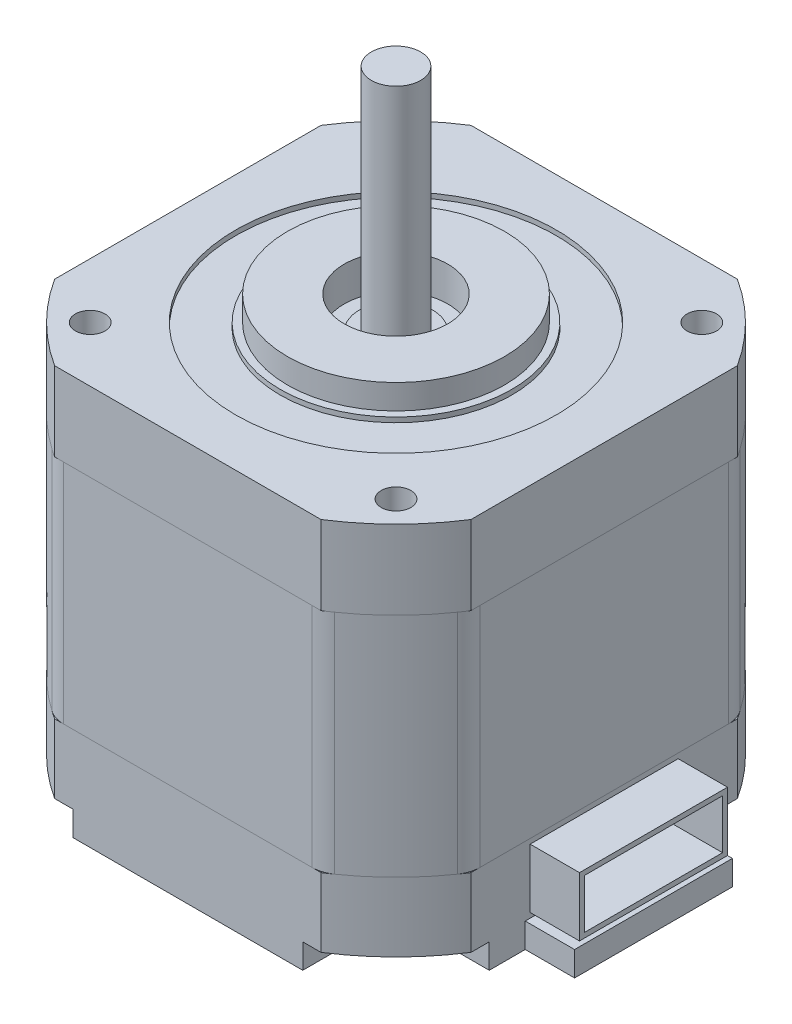
SolidWorks part; units mm, degrees
ref_plane "Alzado" through (0, 0, 0) normal (0, 0, 1) x (1, 0, 0)
ref_plane "Planta" through (0, 0, 0) normal (0, 1, 0) x (1, 0, 0)
ref_plane "Vista lateral" through (0, 0, 0) normal (1, 0, 0) x (0, 0, -1)
sketch "Croquis1" plane through (0, 0, 0) normal (0, 1, 0) x (1, 0, 0)
  line L0 (13.5, 21.1) -> (-13.5, 21.1)
  line L2 (-21.1, 13.5) -> (-21.1, -13.5)
  line L4 (-13.5, -21.1) -> (13.5, -21.1)
  line L6 (21.1, -13.5) -> (21.1, 13.5)
  arc A0 (-13.5, 21.1) -> (-21.1, 13.5) centre (0, 0) ccw
  arc A1 (13.5, 21.1) -> (21.1, 13.5) centre (0, 0) cw
  arc A2 (21.1, -13.5) -> (13.5, -21.1) centre (0, 0) cw
  arc A3 (-21.1, -13.5) -> (-13.5, -21.1) centre (0, 0) ccw
  point P4 (-21.1, 0)
  point P10 (0, 21.1)
  dimension "D2" = 27
  dimension "D1" = 42.2
extrude "Saliente-Extruir1" add sketch "Croquis1" along normal mid plane 23
sketch "Croquis2" plane through (0, 11.5, 0) normal (0, 1, 0) x (1, 0, 0)
  line L12 (13.5003, 21.101) -> (-13.5003, 21.101)
  line L13 (-21.101, 13.5003) -> (-21.101, -13.5003)
  line L14 (-13.5003, -21.101) -> (13.5003, -21.101)
  line L15 (21.101, -13.5003) -> (21.101, 13.5003)
  line L16 (13.5003, 21.101) -> (-13.5003, 21.101)
  line L17 (-21.101, 13.5003) -> (-21.101, -13.5003)
  line L18 (-13.5003, -21.101) -> (13.5003, -21.101)
  line L19 (21.101, -13.5003) -> (21.101, 13.5003)
  arc A12 (21.101, 13.5003) -> (13.5003, 21.101) centre (0, 0) ccw
  arc A13 (-13.5003, 21.101) -> (-21.101, 13.5003) centre (0, 0) ccw
  arc A14 (-21.101, -13.5003) -> (-13.5003, -21.101) centre (0, 0) ccw
  arc A15 (13.5003, -21.101) -> (21.101, -13.5003) centre (0, 0) ccw
  arc A16 (21.101, 13.5003) -> (13.5003, 21.101) centre (0, 0) ccw
  arc A17 (-13.5003, 21.101) -> (-21.101, 13.5003) centre (0, 0) ccw
  arc A18 (-21.101, -13.5003) -> (-13.5003, -21.101) centre (0, 0) ccw
  arc A19 (13.5003, -21.101) -> (21.101, -13.5003) centre (0, 0) ccw
  dimension "D1" = 0.001
fillet "Redondeo1" radius 3 8 edges at (-21.1, 0, -13.5) (-13.5, 0, -21.1) (13.5, 0, -21.1) (21.1, 0, -13.5) (-21.1, 0, 13.5) (-13.5, 0, 21.1) (13.5, 0, 21.1) (21.1, 0, 13.5)
extrude "Saliente-Extruir2" add sketch "Croquis2" along normal blind 8
sketch "Croquis3" plane through (0, -11.5, 0) normal (0, -1, 0) x (1, 0, 0)
  line L8 (-13.5003, -21.101) -> (13.5003, -21.101)
  line L9 (-21.101, 13.5003) -> (-21.101, -13.5003)
  line L10 (13.5003, 21.101) -> (-13.5003, 21.101)
  line L11 (21.101, -13.5003) -> (21.101, 13.5003)
  line L12 (-13.5003, -21.101) -> (13.5003, -21.101)
  line L13 (-21.101, 13.5003) -> (-21.101, -13.5003)
  line L14 (13.5003, 21.101) -> (-13.5003, 21.101)
  line L15 (21.101, -13.5003) -> (21.101, 13.5003)
  arc A8 (13.5003, -21.101) -> (21.101, -13.5003) centre (0, 0) ccw
  arc A9 (-21.101, -13.5003) -> (-13.5003, -21.101) centre (0, 0) ccw
  arc A10 (-13.5003, 21.101) -> (-21.101, 13.5003) centre (0, 0) ccw
  arc A11 (21.101, 13.5003) -> (13.5003, 21.101) centre (0, 0) ccw
  arc A12 (13.5003, -21.101) -> (21.101, -13.5003) centre (0, 0) ccw
  arc A13 (-21.101, -13.5003) -> (-13.5003, -21.101) centre (0, 0) ccw
  arc A14 (-13.5003, 21.101) -> (-21.101, 13.5003) centre (0, 0) ccw
  arc A15 (21.101, 13.5003) -> (13.5003, 21.101) centre (0, 0) ccw
  dimension "D1" = 0
extrude "Saliente-Extruir3" add sketch "Croquis3" along normal blind 9.5
sketch "Croquis4" plane through (0, 19.5, 0) normal (0, 1, 0) x (1, 0, 0)
  line L0 (-15.5, 15.5) -> (-15.5, 21.101) construction
  line L1 (-15.5, 15.5) -> (-21.101, 15.5) construction
  line L2 (-21.101, 13.5003) -> (-21.101, -13.5003) construction
  line L3 (13.5003, 21.101) -> (-13.5003, 21.101) construction
  line L4 (0, 0) -> (0, 21.101) construction
  line L5 (0, 0) -> (-21.101, 0) construction
  circle A0 centre (0, 0) radius 16.25
  circle A1 centre (0, 0) radius 11.75
  circle A2 centre (0, 0) radius 11
  circle A3 centre (-15.5, 15.5) radius 1.5
  circle A7 centre (-15.5, -15.5) radius 1.5
  circle A8 centre (15.5, -15.5) radius 1.5
  circle A9 centre (15.5, 15.5) radius 1.5
  dimension "D1" = 32.5
  dimension "D2" = 23.5
  dimension "D3" = 22
  dimension "D4" = 3
  dimension "D5" = 31
extrude "Cortar-Extruir1" cut sketch "Croquis4" against normal blind 0.5 contours A0 A1 region at (-15.7904, 19.5, 0)
extrude "Saliente-Extruir4" add sketch "Croquis4<3>" along normal blind 2.5 contours A2
sketch "Croquis4<3>" plane through (0, 19.5, 0) normal (0, 1, 0) x (1, 0, 0) same geometry as "Croquis4"
extrude "Cortar-Extruir2" cut sketch "Croquis4<4>" against normal blind 5.5 contours A3 | A9 | A8 | A7
sketch "Croquis4<4>" plane through (0, 19.5, 0) normal (0, 1, 0) x (1, 0, 0) same geometry as "Croquis4"
sketch "Croquis5" plane through (0, 22, 0) normal (0, 1, 0) x (1, 0, 0)
  circle A0 centre (0, 0) radius 5.25
  dimension "D1" = 10.5
extrude "Cortar-Extruir3" cut sketch "Croquis5" against normal blind 3.5
sketch "Croquis6" plane through (0, 18.5, 0) normal (0, 1, 0) x (1, 0, 0)
  circle A0 centre (0, 0) radius 2.5
  circle A1 centre (0, 0) radius 3.7
  dimension "D2" = 5
  dimension "D1" = 1.2
extrude "Saliente-Extruir5" add sketch "Croquis6" along normal blind 0.25
extrude "Saliente-Extruir6" add sketch "Croquis6<2>" along normal blind 23.5 contours A0 region at (0, 18.5, 0)
sketch "Croquis6<2>" plane through (0, 18.5, 0) normal (0, 1, 0) x (1, 0, 0) same geometry as "Croquis6"
sketch "Croquis7" plane through (0, -21, 0) normal (0, -1, 0) x (1, 0, 0)
  line L0 (-11.6503, 21.101) -> (-11.6503, 14.6503)
  line L1 (-21.101, 11.6503) -> (-14.6503, 11.6503)
  line L2 (-21.101, 0) -> (0, 0) construction
  line L3 (0, 0) -> (0, 21.101) construction
  line L4 (21.101, -13.5003) -> (21.101, 13.5003)
  line L5 (13.5003, 21.101) -> (-13.5003, 21.101)
  line L6 (-21.101, 13.5003) -> (-21.101, -13.5003)
  line L7 (-13.5003, -21.101) -> (13.5003, -21.101)
  line L9 (-11.6503, 21.101) -> (-13.5003, 21.101)
  line L10 (-21.101, 13.5003) -> (-21.101, 11.6503)
  line L12 (-21.101, 13.5003) -> (-21.101, -13.5003) construction
  line L13 (13.5003, 21.101) -> (-13.5003, 21.101) construction
  line L14 (-11.6503, -21.101) -> (-11.6503, -14.6503)
  line L15 (-21.101, -11.6503) -> (-14.6503, -11.6503)
  line L16 (-21.101, -13.5003) -> (-21.101, -11.6503)
  line L17 (-11.6503, -21.101) -> (-13.5003, -21.101)
  line L18 (11.6503, -21.101) -> (11.6503, -14.6503)
  line L19 (11.6503, -21.101) -> (13.5003, -21.101)
  line L20 (21.101, -13.5003) -> (21.101, -11.6503)
  line L21 (21.101, -11.6503) -> (14.6503, -11.6503)
  line L22 (11.6503, 21.101) -> (11.6503, 14.6503)
  line L23 (21.101, 11.6503) -> (14.6503, 11.6503)
  line L24 (21.101, 13.5003) -> (21.101, 11.6503)
  line L25 (11.6503, 21.101) -> (13.5003, 21.101)
  arc A0 (-11.6503, 14.6503) -> (-14.6503, 11.6503) centre (-14.6503, 14.6503) cw
  arc A1 (-11.6503, -14.6503) -> (-14.6503, -11.6503) centre (-14.6503, -14.6503) ccw
  arc A2 (-13.5003, -21.101) -> (-21.101, -13.5003) centre (0, 0) cw
  arc A3 (13.5003, -21.101) -> (21.101, -13.5003) centre (0, 0) ccw
  arc A4 (13.5003, -21.101) -> (21.101, -13.5003) centre (0, 0) ccw
  arc A5 (21.101, 13.5003) -> (13.5003, 21.101) centre (0, 0) ccw
  arc A6 (-13.5003, 21.101) -> (-21.101, 13.5003) centre (0, 0) ccw
  arc A7 (-21.101, -13.5003) -> (-13.5003, -21.101) centre (0, 0) ccw
  arc A10 (-13.5003, 21.101) -> (-21.101, 13.5003) centre (0, 0) ccw
  arc A12 (11.6503, -14.6503) -> (14.6503, -11.6503) centre (14.6503, -14.6503) cw
  arc A13 (11.6503, 14.6503) -> (14.6503, 11.6503) centre (14.6503, 14.6503) ccw
  arc A14 (13.5003, 21.101) -> (21.101, 13.5003) centre (0, 0) cw
  dimension "D3" = 3
  dimension "D2" = 1.85
  dimension "D1" = 0
extrude "Cortar-Extruir4" cut sketch "Croquis7" against normal blind 2.5
sketch "Croquis8" plane through (0, -18.5, 0) normal (0, -1, 0) x (1, 0, 0)
  circle A0 centre (15.5, -15.5) radius 1.5 construction
  circle A1 centre (-15.5, -15.5) radius 1.5 construction
  circle A2 centre (-15.5, 15.5) radius 1.5 construction
  circle A3 centre (15.5, 15.5) radius 1.5 construction
  circle A4 centre (15.5, -15.5) radius 1.5
  circle A5 centre (-15.5, -15.5) radius 1.5
  circle A6 centre (-15.5, 15.5) radius 1.5
  circle A7 centre (15.5, 15.5) radius 1.5
extrude "Cortar-Extruir5" cut sketch "Croquis8" against normal blind 15
sketch "Croquis9" plane through (0, -21, 0) normal (0, -1, 0) x (1, 0, 0)
  circle A2 centre (0, 0) radius 4.2
  circle A3 centre (0, 0) radius 4.2
  dimension "D1" = 0.5
extrude "Cortar-Extruir6" cut sketch "Croquis9" against normal blind 3
sketch "Croquis10" plane through (0, -18, 0) normal (0, -1, 0) x (1, 0, 0)
  circle A0 centre (0, 0) radius 2.5 construction
  circle A1 centre (0, 0) radius 3.7
  circle A2 centre (0, 0) radius 3.7
  circle A3 centre (0, 0) radius 2.5
  dimension "D1" = 0
extrude "Saliente-Extruir7" add sketch "Croquis10" along normal blind 0.25
extrude "Saliente-Extruir8" add sketch "Croquis10<2>" along normal blind 1.25 contours A3 region at (0, -18, 0)
sketch "Croquis10<2>" plane through (0, -18, 0) normal (0, -1, 0) x (1, 0, 0) same geometry as "Croquis10"
sketch "Croquis11" plane through (21.101, 0, 0) normal (1, 0, 0) x (0, 0, -1)
  line L0 (-12.5919, -11.5) -> (12.5919, -11.5) construction
  line L1 (8, -21) -> (-8, -21)
  line L2 (8, -21) -> (8, -18.5)
  line L3 (8, -18.5) -> (-8, -18.5)
  line L4 (-8, -21) -> (-8, -18.5)
  line L5 (-21.101, -18.5) -> (-13.5003, -18.5) construction
  line L6 (11.6503, -21) -> (-11.6503, -21) construction
  line L7 (8, -18.5) -> (-8, -18.5)
  line L8 (8, -18.5) -> (8, -11.5)
  line L9 (8, -11.5) -> (-8, -11.5)
  line L10 (-8, -18.5) -> (-8, -11.5)
  line L11 (7.5, -18) -> (7.5, -12)
  line L12 (7.5, -12) -> (-7.5, -12)
  line L13 (-7.5, -18) -> (-7.5, -12)
  line L14 (7.5, -18) -> (-7.5, -18)
  line L15 (7, -17.5) -> (7, -12.5)
  line L16 (7, -12.5) -> (-7, -12.5)
  line L17 (-7, -17.5) -> (-7, -12.5)
  line L18 (7, -17.5) -> (-7, -17.5)
  point P0 (0, -16.25)
  point P5 (0, -11.5)
  point P14 (0, -18.5)
  line M15 (-11.6503, -21) -> (11.6503, -21)
  dimension "D1" = 16
  dimension "D2" = 0.5
  dimension "D3" = 0.5
extrude "Saliente-Extruir9" add sketch "Croquis11" along normal blind 5 contours L14 L11 L12 L13 L15 L18 L17 L16 | L4 L2 L3 M15 region at (21.101, -19.75, 0) region at (21.101, -17.8384, 0)
